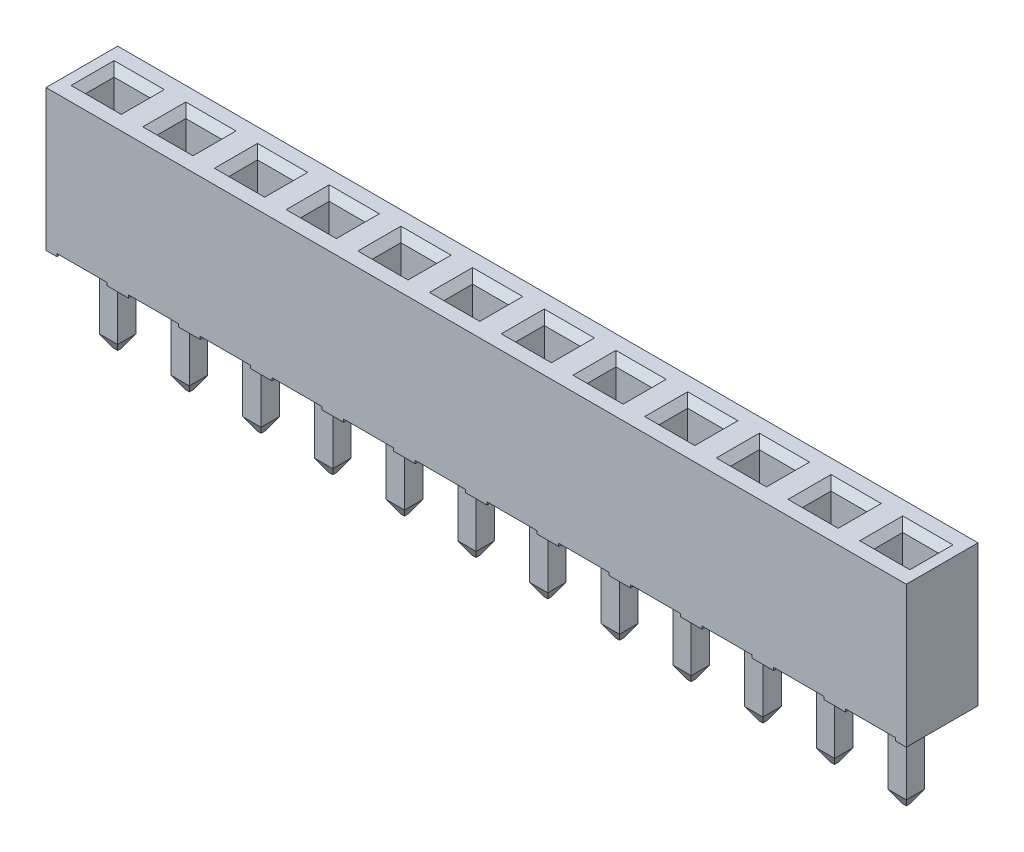
SolidWorks part; units mm, degrees
note: '?' marks a value the reader was unsure of.
ref_plane "Front Plane" through (0, 0, 0) normal (0, 0, 1) x (1, 0, 0)
ref_plane "Top Plane" through (0, 0, 0) normal (0, 1, 0) x (1, 0, 0)
ref_plane "Right Plane" through (0, 0, 0) normal (1, 0, 0) x (0, 0, -1)
sketch "Sketch1" plane through (0, 0, 0) normal (0, 1, 0) x (1, 0, 0)
  line L1 (-1.27, 1.27) -> (1.27, 1.27)
  line L2 (-1.27, 1.27) -> (-1.27, -1.27)
  line L3 (-1.27, -1.27) -> (1.27, -1.27)
  line L4 (1.27, 1.27) -> (1.27, -1.27)
  line L5 (-1.27, 1.27) -> (1.27, -1.27) construction
  line L6 (-1.27, -1.27) -> (1.27, 1.27) construction
  point P0 (0, 0)
  dimension "D1" = 2.54
extrude "Boss-Extrude1" add sketch "Sketch1" along normal blind 4.9
sketch "Sketch2" plane through (0, 4.9, 0) normal (0, 1, 0) x (1, 0, 0)
  line L1 (0.635, 0.508) -> (-0.635, 0.508)
  line L2 (0.635, 0.508) -> (0.635, -0.508)
  line L3 (0.635, -0.508) -> (-0.635, -0.508)
  line L4 (-0.635, 0.508) -> (-0.635, -0.508)
  line L5 (0.635, 0.508) -> (-0.635, -0.508) construction
  line L6 (0.635, -0.508) -> (-0.635, 0.508) construction
  point P0 (0, 0)
  dimension "D1" = 1.27
  dimension "D2" = 1.016
extrude "Cut-Extrude1" cut sketch "Sketch2" against normal offset from surface (3.63 mm away) 1.27 up to face at (0, 0, 0)
chamfer "Chamfer1" distance 0.254 angle 45 4 edges at (0.635, 4.9, 0) (0, 4.9, 0.508) (-0.635, 4.9, 0) (0, 4.9, -0.508)
sketch "Sketch3" plane through (0, 0, 0) normal (0, -1, 0) x (1, 0, 0)
  line L0 (1.27, -1.27) -> (-1.27, -1.27) construction
  line L1 (-1.27, 1.27) -> (-0.889, 1.27)
  line L2 (-1.27, 1.27) -> (-1.27, -1.27)
  line L3 (-1.27, -1.27) -> (-0.889, -1.27)
  line L4 (-0.889, 1.27) -> (-0.889, -1.27)
  line L6 (1.27, 1.27) -> (0.889, 1.27)
  line L7 (1.27, 1.27) -> (1.27, -1.27)
  line L8 (1.27, -1.27) -> (0.889, -1.27)
  line L9 (0.889, 1.27) -> (0.889, -1.27)
  dimension "D1" = 0.381
extrude "Boss-Extrude2" add sketch "Sketch3" along normal offset from surface (0.1 mm away) 5 up to face at (0, 4.9, 0)
sketch "Sketch4" plane through (0, 0, 0) normal (0, -1, 0) x (1, 0, 0)
  line L1 (0.325, 0.325) -> (-0.325, 0.325)
  line L2 (0.325, 0.325) -> (0.325, -0.325)
  line L3 (0.325, -0.325) -> (-0.325, -0.325)
  line L4 (-0.325, 0.325) -> (-0.325, -0.325)
  line L5 (0.325, 0.325) -> (-0.325, -0.325) construction
  line L6 (0.325, -0.325) -> (-0.325, 0.325) construction
  point P0 (0, 0)
  dimension "D1" = 0.65
extrude "Boss-Extrude3" add sketch "Sketch4" along normal offset from surface (3.1 mm away) 3 up to face at (-1.0795, -0.1, 0) offset beyond the face yes
chamfer "Chamfer2" distance 0.254 angle 60 4 edges at (-0.325, -3.1, 0) (0, -3.1, 0.325) (0.325, -3.1, 0) (0, -3.1, -0.325)
pattern_linear "LPattern1" count 12 spacing 2.54 along (-1, 0, 0) of "Chamfer2", "Boss-Extrude3", "Boss-Extrude2", "Chamfer1", "Cut-Extrude1", "Boss-Extrude1"
ref_point "Point1"
ref_point "Point2"
ref_axis "Axis1" through (-27.94, -4.2225, 0) along (0, 1, 0)?
ref_axis "Axis2" through (0, -3.7118, 0) along (0, 1, 0)?
